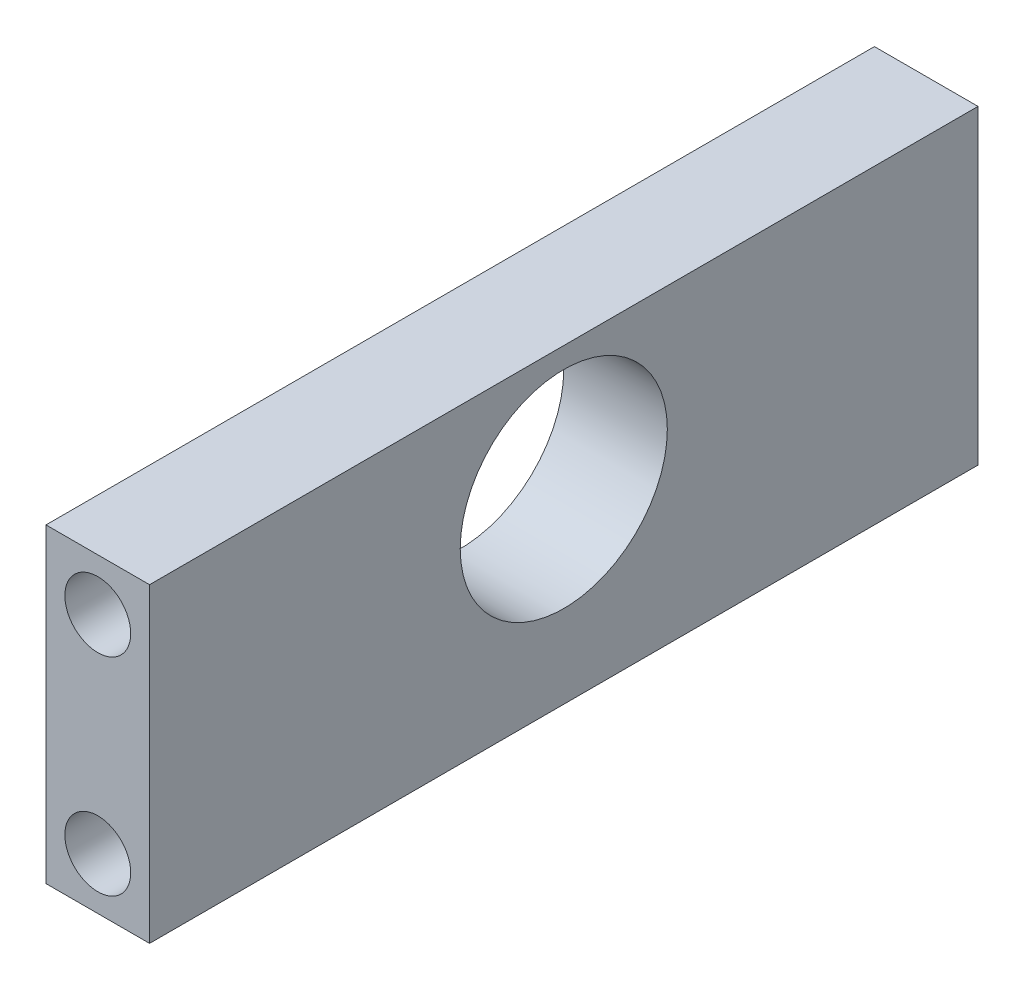
SolidWorks part; units mm, degrees
ref_plane "Front Plane" through (0, 0, 0) normal (0, 0, 1) x (1, 0, 0)
ref_plane "Top Plane" through (0, 0, 0) normal (0, 1, 0) x (1, 0, 0)
ref_plane "Right Plane" through (0, 0, 0) normal (1, 0, 0) x (0, 0, -1)
sketch "Sketch1" plane through (0, 0, 0) normal (1, 0, 0) x (0, 0, -1)
  line L1 (-25.4, -9.525) -> (25.4, -9.525)
  line L2 (-25.4, -9.525) -> (-25.4, 9.525)
  line L3 (-25.4, 9.525) -> (25.4, 9.525)
  line L4 (25.4, -9.525) -> (25.4, 9.525)
  line L5 (-25.4, -9.525) -> (25.4, 9.525) construction
  line L6 (-25.4, 9.525) -> (25.4, -9.525) construction
  point P0 (0, 0)
  dimension "D1" = 50.8
  dimension "D2" = 19.05
extrude "Boss-Extrude1" add sketch "Sketch1" along normal blind 6.35
hole_wizard "1/2 (0.5) Diameter Hole1" positions "Sketch9" profile "Sketch8" hole size "1/2" standard "ANSI Inch"
sketch "Sketch9" plane through (6.35, 0, 0) normal (1, 0, 0) x (0, 0, -1)
  line L0 (-25.4, -9.525) -> (25.4, -9.525) construction
  point P0 (0, 1.905)
  dimension "D1" = 11.43
sketch "Sketch8" plane through (6.35, 1.905, 0) normal (0, 1, 0) x (0, 0, -1)
  line L0 (0, 0) -> (0, 73.9195)
  line L1 (0, 73.9195) -> (6.35, 70.104)
  line L2 (6.35, 70.104) -> (6.35, 0)
  line L5 (6.35, 0) -> (0, 0)
  line L10 (0, 73.9195) -> (-6.35, 70.104) construction
  line L11 (0, -6.35) -> (0, 107.95) construction
  dimension "Hole Dia." = 12.7
  dimension "Hole Depth" = 70.104
  dimension "Drill Angle" = 118
hole_wizard "#10-32 Tapped Hole1" positions "Sketch11" profile "Sketch10" tap size "#10-32" standard "ANSI Inch"
sketch "Sketch11" plane through (-0.103, -5.3339, 25.4) normal (0, 0, -1) x (-1, 0, 0)
  line L0 (-6.453, 14.8589) -> (-0.103, 14.8589) construction
  line L2 (-6.453, -4.1911) -> (-0.103, -4.1911) construction
  line L3 (-6.453, 14.8589) -> (-0.103, 14.8589) construction
  point P0 (-3.278, -1.0161)
  point P2 (-3.278, 11.6839)
  point P6 (-3.278, 14.8589)
  dimension "D1" = 0
  dimension "D2" = 0
  dimension "D3" = 3.175
  dimension "D4" = 3.175
sketch "Sketch10" plane through (3.175, -6.35, 25.4) normal (1, 0, 0) x (0, -1, 0)
  line L0 (0, 0) -> (0, 13.1513)
  line L1 (0, 13.1513) -> (2.0193, 11.938)
  line L2 (2.0193, 11.938) -> (2.0193, 0)
  line L5 (2.0193, 0) -> (0, 0)
  line L10 (0, 13.1513) -> (-2.0193, 11.938) construction
  line L11 (0, -6.35) -> (0, 107.95) construction
  dimension "Tap Drill Dia." = 4.0386
  dimension "Tap Drill Depth" = 11.938
  dimension "Drill Angle" = 118
cosmetic thread "Hole Thread1" parameters "D1"=9.652, "D2"=4.826
cosmetic thread "Hole Thread2" parameters "D1"=9.652, "D2"=4.826
